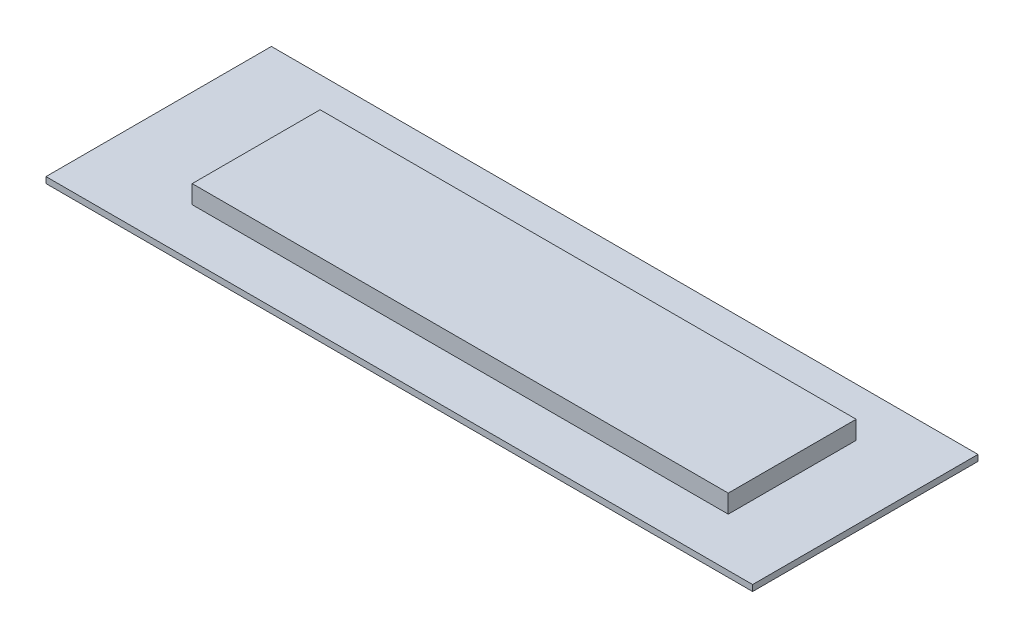
SolidWorks part; units mm, degrees
ref_plane "Front" through (0, 0, 0) normal (0, 0, 1) x (1, 0, 0)
ref_plane "Top" through (0, 0, 0) normal (0, 1, 0) x (1, 0, 0)
ref_plane "Right" through (0, 0, 0) normal (1, 0, 0) x (0, 0, -1)
sketch "Sketch1" plane through (0, 0, 0) normal (0, 1, 0) x (1, 0, 0)
  line L1 (-58, 18.5) -> (58, 18.5)
  line L2 (-58, 18.5) -> (-58, -18.5)
  line L3 (-58, -18.5) -> (58, -18.5)
  line L4 (58, 18.5) -> (58, -18.5)
  line L5 (-58, 18.5) -> (58, -18.5) construction
  line L6 (-58, -18.5) -> (58, 18.5) construction
  point P0 (0, 0)
  dimension "D1" = 37
  dimension "D2" = 116
extrude "Boss-Extrude1" add sketch "Sketch1" along normal blind 1
sketch "Sketch2" plane through (0, 1, 0) normal (0, 1, 0) x (1, 0, 0)
  line L0 (-58, 18.5) -> (-58, -18.5) construction
  line L1 (-42, 10.5) -> (46, 10.5)
  line L2 (-42, 10.5) -> (-42, -10.5)
  line L3 (-42, -10.5) -> (46, -10.5)
  line L4 (46, 10.5) -> (46, -10.5)
  line L5 (-42, 10.5) -> (46, -10.5) construction
  line L6 (-42, -10.5) -> (46, 10.5) construction
  point P0 (2, 0)
  dimension "D1" = 21
  dimension "D2" = 0
  dimension "D3" = 88
  dimension "D4" = 16
extrude "Boss-Extrude2" add sketch "Sketch2" along normal blind 3
